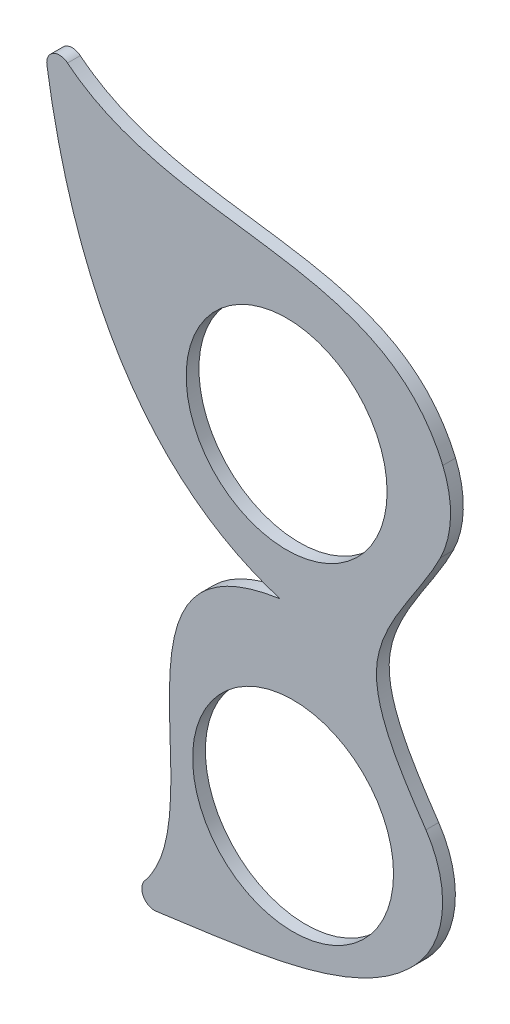
SolidWorks part; units mm, degrees
ref_plane "前视基准面" through (0, 0, 0) normal (0, 0, 1) x (1, 0, 0)
ref_plane "上视基准面" through (0, 0, 0) normal (0, 1, 0) x (1, 0, 0)
ref_plane "右视基准面" through (0, 0, 0) normal (1, 0, 0) x (0, 0, -1)
sketch "草图1" plane through (0, 0, 0) normal (0, 0, 1) x (1, 0, 0)
  line L0 (190.2671, -255.6319) -> (190.2671, 280.038) construction
  line L1 (190.2671, 151.1136) -> (190.2671, -81.8904)
  circle A1 centre (59.3394, 138.617) radius 78.74
  circle A2 centre (64.3919, -118.0819) radius 78.74
  spline S0 degree 3 poles (190.2671, 151.1136) (155.7868, 310.3964) (-48.4361, 217.1499) (-132.4559, 325.0272) knots 0 0 0 0 1 1 1 1
  spline S1 degree 3 poles (-132.4559, 325.0272) (-119.3943, 206.4975) (-75.4976, 64.089) (54.2159, 24.2036) knots 0 0 0 0 1 1 1 1
  spline S2 degree 3 poles (54.2159, 24.2036) (-114.6225, -0.5548) (39.7836, -196.6781) (-88.1381, -245.0604) knots 0 0 0 0 1 1 1 1
  spline S3 degree 3 poles (-88.1381, -245.0604) (6.7799, -220.2608) (192.982, -238.7627) (190.2671, -81.8904) knots 0 0 0 0 1 1 1 1
  point P3 (190.2671, 12.2031)
extrude "凸台-拉伸1" add sketch "草图1" along normal blind 10
sketch "草图2" plane through (0, 0, 10) normal (0, 0, 1) x (1, 0, 0)
  line L1 (188.8963, -107.3939) -> (205.8629, -98.6797)
  line L2 (205.8629, -98.6797) -> (202.34, 151.1184)
  line L3 (202.34, 151.1184) -> (190.2661, 151.1184)
  spline S0 degree 3 poles (190.2661, 151.1184) (188.5444, 103.2768) (81.5183, 21.8325) (169.0631, -71.6122) (188.8963, -107.3939) knots 0 0 0 0 0.52242 1 1 1 1
  spline S1 degree 3 poles (190.2671, 151.1136) (155.7868, 310.3964) (-48.4361, 217.1499) (-132.4559, 325.0272) knots 0 0 0 0 1 1 1 1 construction
  spline S2 degree 3 poles (-88.1381, -245.0604) (6.7799, -220.2608) (192.982, -238.7627) (190.2671, -81.8904) knots 0 0 0 0 1 1 1 1 construction
extrude "切除-拉伸1" cut sketch "草图2" against normal blind 10
fillet "圆角1" radius 76.2 2 edges at (190.2661, 151.1184, 5) (188.8963, -107.3939, 5)
fillet "圆角2" radius 10 1 edges at (-132.4559, 325.0272, 5)
fillet "圆角3" radius 10 1 edges at (-88.1381, -245.0604, 5)
